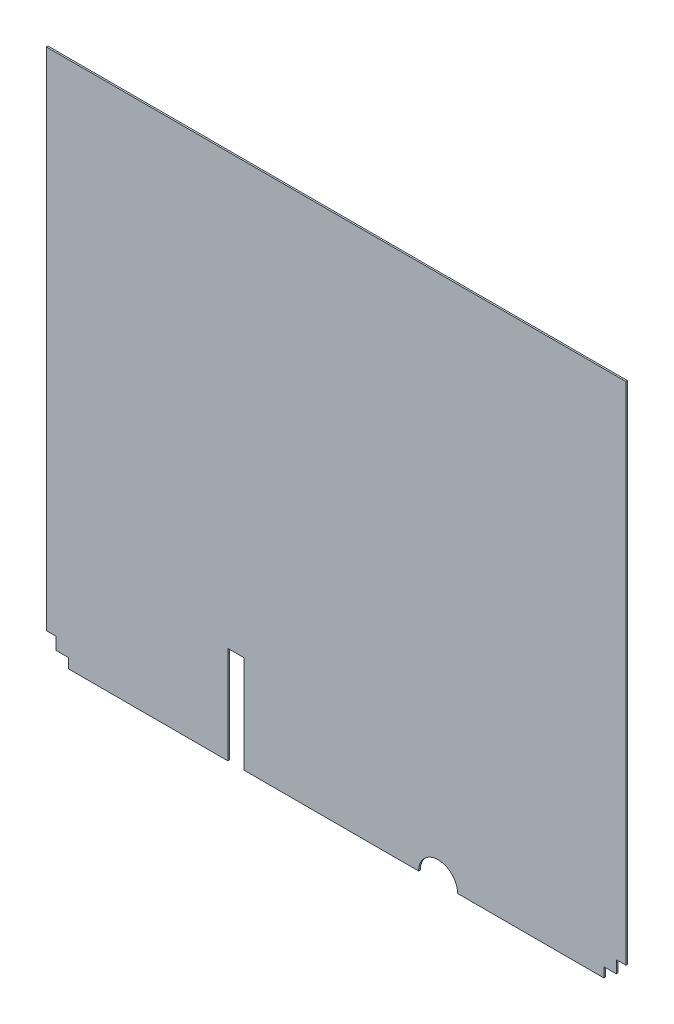
SolidWorks part; units mm, degrees
ref_plane "Front Plane" through (0, 0, 0) normal (0, 0, 1) x (1, 0, 0)
ref_plane "Top Plane" through (0, 0, 0) normal (0, 1, 0) x (1, 0, 0)
ref_plane "Right Plane" through (0, 0, 0) normal (1, 0, 0) x (0, 0, -1)
sketch "Sketch1" plane through (0, 0, 0) normal (0, 0, 1) x (1, 0, 0)
  line L0 (0, 34.544) -> (15.24, 34.544)
  line L1 (0, 0) -> (907.001, 0)
  line L2 (0, 0) -> (0, 825.5)
  line L3 (0, 825.5) -> (907.001, 825.5)
  line L4 (907.001, 0) -> (907.001, 825.5)
  line L5 (0, 0) -> (914.4, 0) construction
  line L6 (0, 0) -> (0, 914.4) construction
  line L7 (0, 914.4) -> (914.4, 914.4) construction
  line L8 (914.4, 0) -> (914.4, 914.4) construction
  line L9 (15.24, 34.544) -> (15.24, 15.24)
  line L10 (15.24, 15.24) -> (34.544, 15.24)
  line L11 (34.544, 15.24) -> (34.544, 0)
  line L12 (907.001, 34.544) -> (891.761, 34.544)
  line L13 (891.761, 34.544) -> (891.761, 15.24)
  line L14 (891.761, 15.24) -> (872.457, 15.24)
  line L15 (872.457, 15.24) -> (872.457, 0)
  line L16 (283.8375, 0) -> (283.8375, 152.4)
  line L17 (283.8375, 152.4) -> (309.2375, 152.4)
  line L18 (309.2375, 152.4) -> (309.2375, 0)
  arc A0 (643.4983, 0) -> (582.5383, 0) centre (613.0183, 0) ccw
  dimension "D13" = 30.48
  dimension "D1" = 825.5
  dimension "D2" = 907.001
  dimension "D3" = 914.4
  dimension "D4" = 914.4
  dimension "D5" = 15.24
  dimension "D6" = 15.24
  dimension "D7" = 34.544
  dimension "D8" = 34.544
  dimension "D9" = 15.24
  dimension "D10" = 15.24
  dimension "D11" = 34.544
  dimension "D12" = 34.544
  dimension "D14" = 152.4
  dimension "D15" = 25.4
extrude "Boss-Extrude1" add sketch "Sketch1" along normal blind 2.54 contours L15 L14 L13 L12 L4 L3 L2 L0 L9 L10 L11 L1 region at (454.0058, 416.1756, 0)
